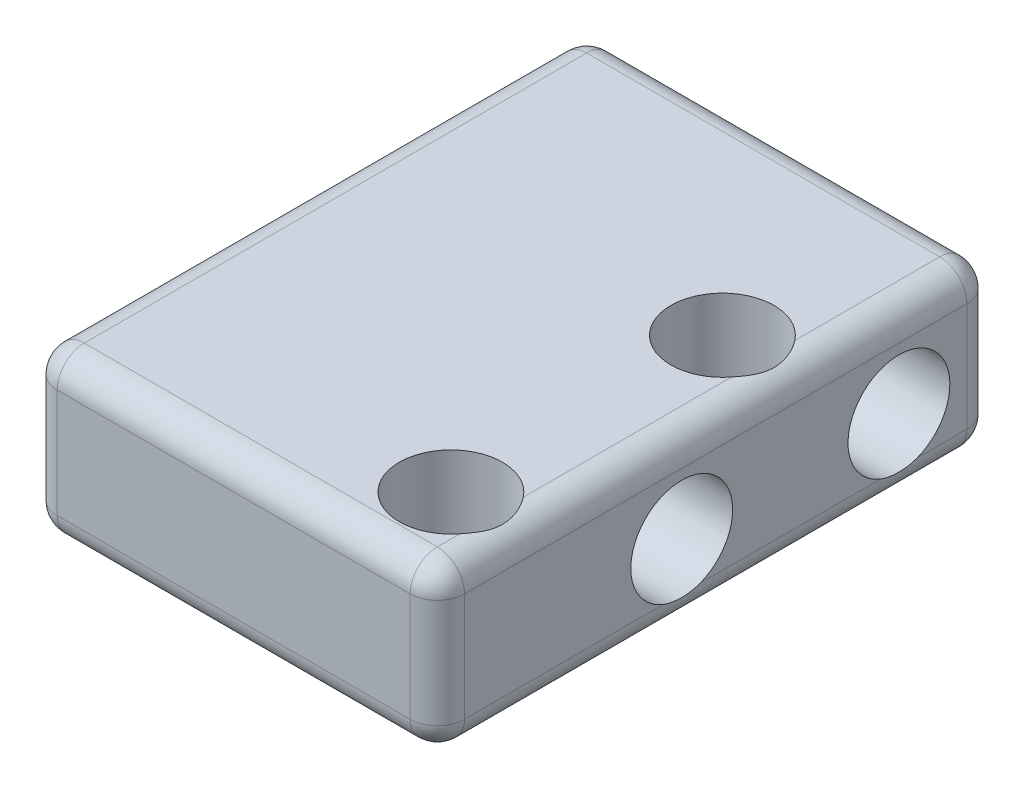
SolidWorks part; units mm, degrees
ref_plane "Front Plane" through (0, 0, 0) normal (0, 0, 1) x (1, 0, 0)
ref_plane "Top Plane" through (0, 0, 0) normal (0, 1, 0) x (1, 0, 0)
ref_plane "Right Plane" through (0, 0, 0) normal (1, 0, 0) x (0, 0, -1)
sketch "Sketch1" plane through (0, 0, 0) normal (0, 1, 0) x (1, 0, 0)
  line L1 (0, 0) -> (-30, 0)
  line L2 (0, 0) -> (0, 41)
  line L3 (0, 41) -> (-30, 41)
  line L4 (-30, 0) -> (-30, 41)
  circle A0 centre (-5, 6) radius 2.25
  circle A1 centre (-5, 26) radius 2.25
  point P9 (0, 0)
  dimension "D2" = 20
  dimension "D3" = 15
  dimension "D4" = 4.5
  dimension "D5" = 5
  dimension "D1" = 6
  dimension "D6" = 25
extrude "Boss-Extrude1" add sketch "Sketch1" along normal blind 12
sketch "Sketch3" plane through (0, 12, 0) normal (0, 1, 0) x (1, 0, 0)
  circle A0 centre (-5, 26) radius 3.8
  circle A1 centre (-5, 6) radius 3.8
  dimension "D1" = 7.6
extrude "Cut-Extrude2" cut sketch "Sketch3" against normal offset from surface (7 mm away) 5 up to face at (-15, 0, -20.5)
fillet "Fillet1" radius 2 12 edges at (-30, 6, 0) (-15, 12, 0) (0, 6, 0) (-15, 0, 0) (0, 6, -41) (-15, 12, -41) (-30, 6, -41) (-15, 0, -41) (0, 12, -20.5) (-30, 12, -20.5) (0, 0, -20.5) (-30, 0, -20.5)
sketch "Sketch4" plane through (-30, 0, 0) normal (-1, 0, 0) x (0, 0, 1)
  line L1 (-2, 0) -> (-39, 0) construction
  line L2 (0, 10) -> (0, 2) construction
  circle A0 centre (-34, 5.5) radius 2.25
  circle A1 centre (-18, 5.5) radius 2.25
  point P4 (0, 0)
  dimension "D1" = 4.5
  dimension "D2" = 16
  dimension "D4" = 5.5
  dimension "10" = 18
extrude "Cut-Extrude3" cut sketch "Sketch4" against normal through all
sketch "Sketch5" plane through (-30, 0, 0) normal (-1, 0, 0) x (0, 0, 1)
  circle A0 centre (-34, 5.5) radius 3.75
  circle A1 centre (-18, 5.5) radius 3.75
  dimension "D1" = 7.5
extrude "Cut-Extrude4" cut sketch "Sketch5" along direction (1, 0, 0) on the side of the normal offset from surface (6 mm away) 6 from surface up to face at (0, 5.5, -31.75) starting at face at (0, 5.5, -31.75)
